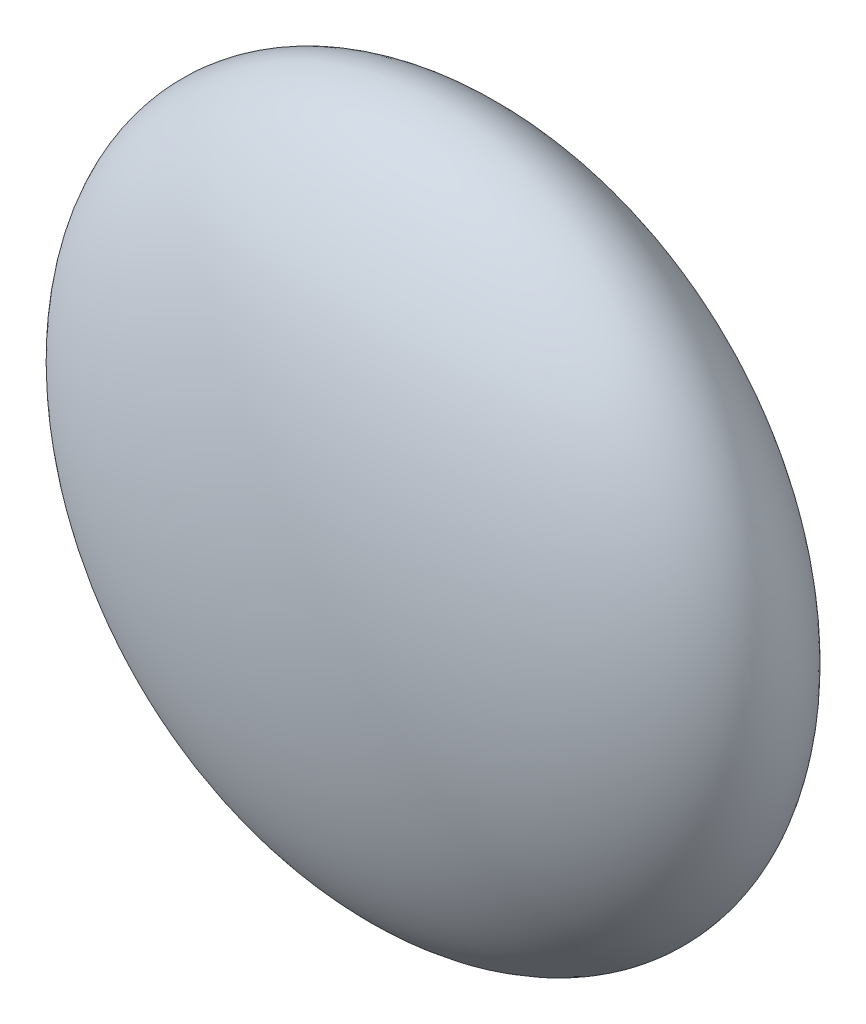
SolidWorks part; units mm, degrees
ref_plane "Front Plane" through (0, 0, 0) normal (0, 0, 1) x (1, 0, 0)
ref_plane "Top Plane" through (0, 0, 0) normal (0, 1, 0) x (1, 0, 0)
ref_plane "Right Plane" through (0, 0, 0) normal (1, 0, 0) x (0, 0, -1)
sketch "Sketch1" plane through (0, 0, 0) normal (1, 0, 0) x (0, 0, -1)
  line L0 (-0.242, 0) -> (0.242, 0)
  line L1 (0, 0.55) -> (0, -0.55) construction
  ellipse E0 centre (0, 0) end of major axis (0, 0.55) minor radius 0.242 (-0.242, 0) -> (0.242, 0) cw
  dimension "D1" = 0.484
  dimension "D2" = 1.1
revolve "Revolve1" add sketch "Sketch1" angle 360 about L0
ref_axis "Axis1" through (0, 0.6875, 0) along (0, -1, 0)
ref_axis "Axis2" through (0.6875, 0, 0) along (-1, 0, 0)
